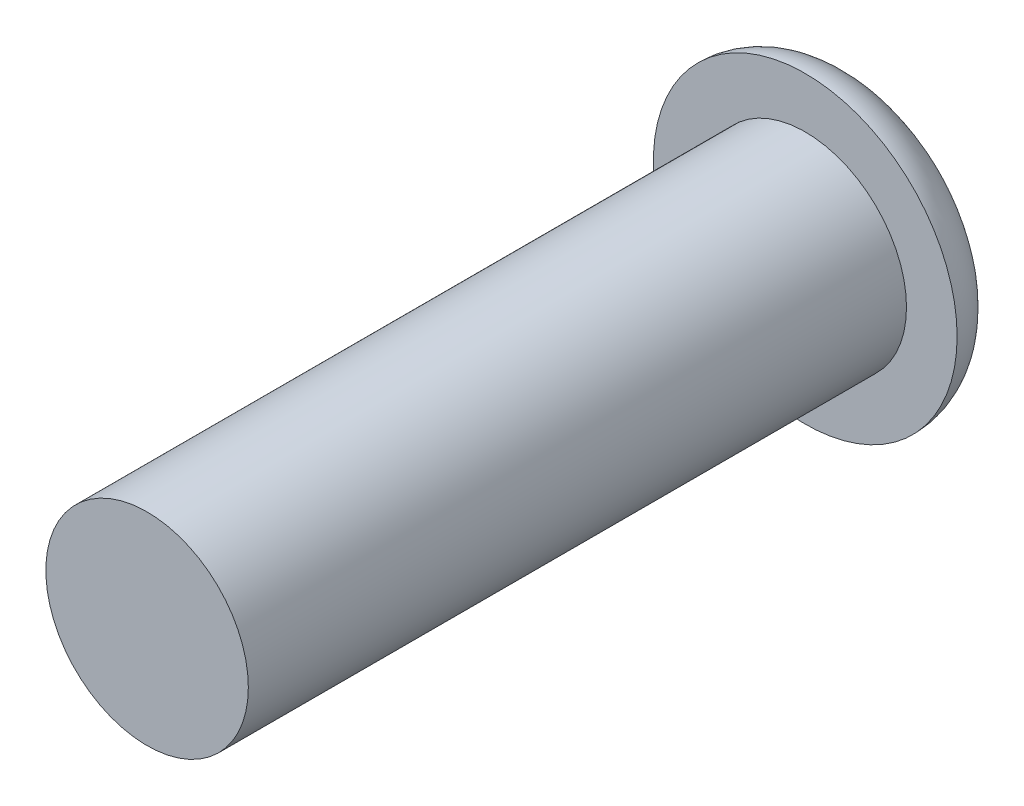
SolidWorks part; units mm, degrees
ref_plane "Front Plane" through (0, 0, 0) normal (0, 0, 1) x (1, 0, 0)
ref_plane "Top Plane" through (0, 0, 0) normal (0, 1, 0) x (1, 0, 0)
ref_plane "Right Plane" through (0, 0, 0) normal (1, 0, 0) x (0, 0, -1)
sketch "Sketch1" plane through (0, 0, 0) normal (0, 0, 1) x (1, 0, 0)
  circle A0 centre (0, 0) radius 15
  dimension "D1" = 30
extrude "Boss-Extrude1" add sketch "Sketch1" along normal blind 5
sketch "Sketch2" plane through (0, 0, 5) normal (0, 0, 1) x (1, 0, 0)
  circle A0 centre (0, 0) radius 10
  dimension "D1" = 20
extrude "Boss-Extrude2" add sketch "Sketch2" along normal blind 65
fillet "Fillet1" radius 5 1 edges at (15, 0, 0)
